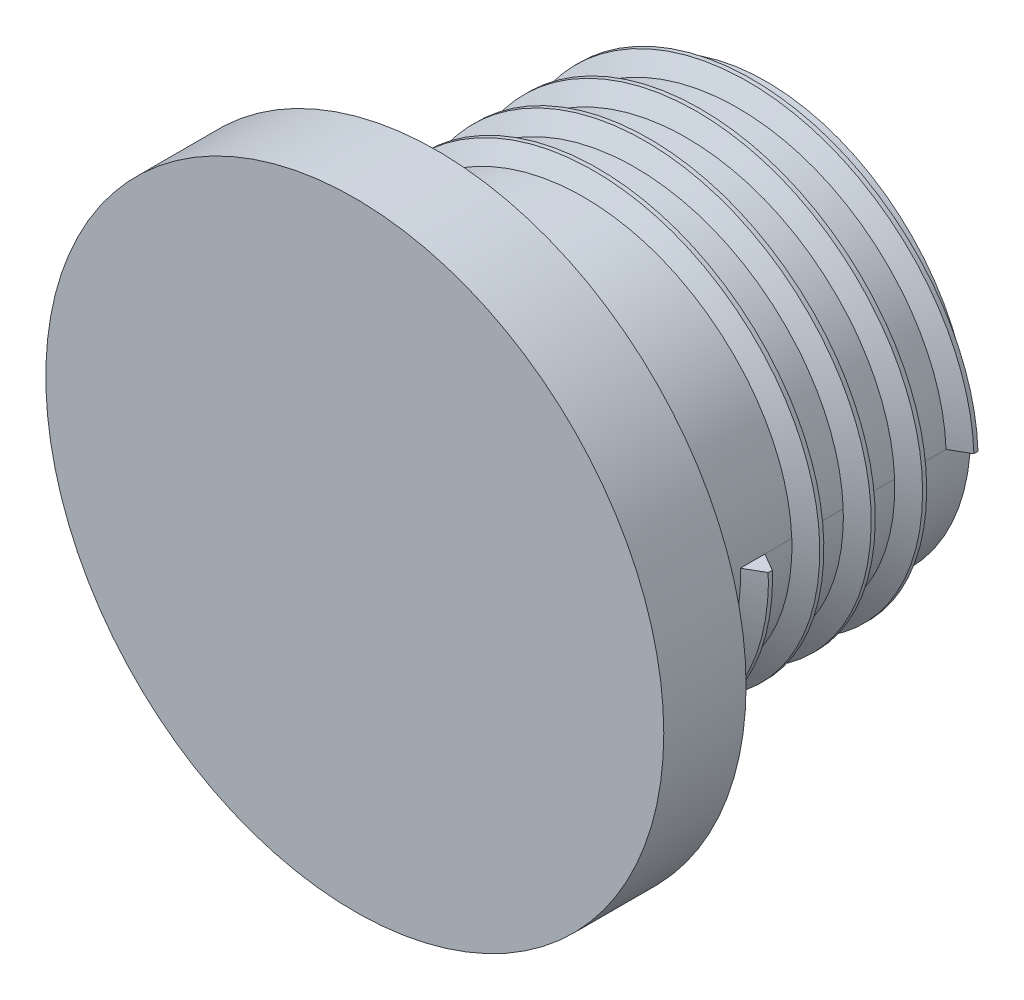
SolidWorks part; units mm, degrees
ref_plane "前基準面" through (0, 0, 0) normal (0, 0, 1) x (1, 0, 0)
ref_plane "上基準面" through (0, 0, 0) normal (0, 1, 0) x (1, 0, 0)
ref_plane "右基準面" through (0, 0, 0) normal (1, 0, 0) x (0, 0, -1)
sketch "草圖1" plane through (0, 0, 0) normal (0, 0, 1) x (1, 0, 0)
  circle A0 centre (0, 0) radius 3.0043
extrude "填料-伸長1" add sketch "草圖1" along normal blind 0.8
sketch "草圖2" plane through (0, 0, 0) normal (0, 0, -1) x (-1, 0, 0)
  circle A0 centre (0, 0) radius 1.9868
extrude "填料-伸長2" add sketch "草圖2" along normal blind 3.2
thread "螺紋2" pitch 0.3175 method extrude profile "螺紋輪廓4" start angle 0, offset 0, length 2, pitch 0.5, diameter 3.9736
ref_plane "平面4" through (1.9868, 0, -3.2) normal (0, -1, 0) x (1, 0, 0)
sketch "螺紋輪廓4" plane through (1.9868, 0, -3.2) normal (0, -1, 0) x (1, 0, 0)
  line L0 (0, 0) -> (0, 0.3175) construction
  line L1 (0, 0) -> (0.1719, 0.0992)
  line L2 (0.1719, 0.0992) -> (0.1719, 0.1389)
  line L3 (0.1719, 0.1389) -> (0, 0.2381)
  line L4 (0.1719, 0.1191) -> (0, 0.1191) construction
  line L11 (0, 0) -> (0, 0.2381)
  point P2 (0, 0)
  dimension "Pitch" = 0.3175
  dimension "Profile_Angle" = 60
  dimension "Profile_Land" = 0.0397
  dimension "Profile_Height" = 0.1719
